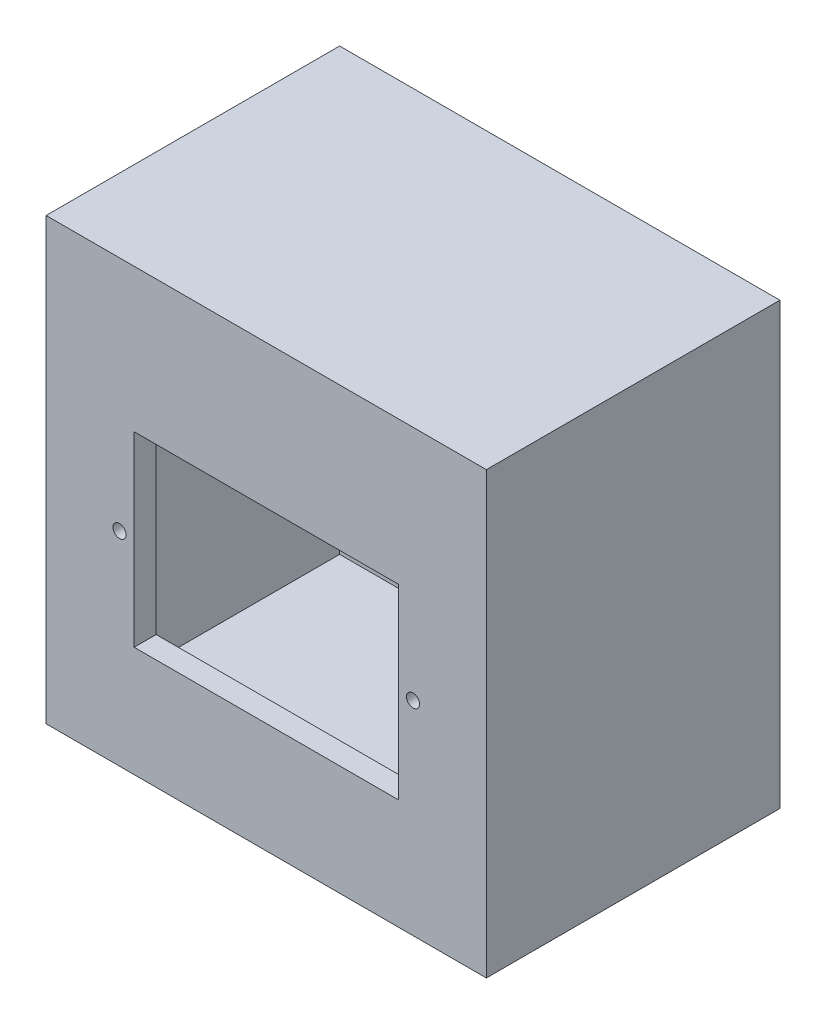
SolidWorks part; units mm, degrees
note: '?' marks a value the reader was unsure of.
ref_plane "Front Plane" through (0, 0, 0) normal (0, 0, 1) x (1, 0, 0)
ref_plane "Top Plane" through (0, 0, 0) normal (0, 1, 0) x (1, 0, 0)
ref_plane "Right Plane" through (0, 0, 0) normal (1, 0, 0) x (0, 0, -1)
sketch "Sketch1" plane through (0, 0, 0) normal (0, 1, 0) x (1, 0, 0)
  line L1 (-38.1, -25.4) -> (38.1, -25.4)
  line L2 (-38.1, -25.4) -> (-38.1, 25.4)
  line L3 (-38.1, 25.4) -> (38.1, 25.4)
  line L4 (38.1, -25.4) -> (38.1, 25.4)
  line L5 (-38.1, -25.4) -> (38.1, 25.4) construction
  line L6 (-38.1, 25.4) -> (38.1, -25.4) construction
  point P0 (0, 0)
  dimension "D1" = 50.8
  dimension "D2" = 76.2
extrude "body" add sketch "Sketch1" along normal blind 76.2
sketch "Sketch2" plane through (0, 0, 25.4) normal (0, 0, 1) x (1, 0, 0)
  line L0 (-38.1, 0) -> (38.1, 0) construction
  line L1 (-22.86, 19.0956) -> (22.86, 19.0956)
  line L2 (-22.86, 19.0956) -> (-22.86, 51.4044)
  line L3 (-22.86, 51.4044) -> (22.86, 51.4044)
  line L4 (22.86, 19.0956) -> (22.86, 51.4044)
  line L5 (-22.86, 19.0956) -> (22.86, 51.4044) construction
  line L6 (-22.86, 51.4044) -> (22.86, 19.0956) construction
  point P0 (0, 35.25)
  point P5 (0, 0)
  dimension "D1" = 32.3088
  dimension "D2" = 45.72
  dimension "D3" = 0
extrude "camera hole" cut sketch "Sketch2" against normal blind 3.81
shell "hollow" thickness 2.54 removed face at (0, 35.25, 21.59)
hole_wizard "#4-40 Tapped Hole1" positions "Sketch4" profile "Sketch3" tap size "#4-40" standard "ANSI Inch"
sketch "Sketch4" plane through (0, 0, 25.4) normal (0, 0, 1) x (1, 0, 0)
  line L1 (22.86, 51.4044) -> (-22.86, 51.4044) construction
  point P0 (-25.4, 35.25)
  point P2 (25.4, 35.25)
  point P14 (0, 51.4044)
  dimension "D1" = 50.8
  dimension "D2" = 25.4
  dimension "D3" = 16.1544
sketch "Sketch3" plane through (-25.4, 35.25, 25.4) normal (1, 0, 0) x (0, -1, 0)
  line L0 (0, 0) -> (0, 48.9382)
  line L1 (0, 48.9382) -> (1.1303, 48.259)
  line L2 (1.1303, 48.259) -> (1.1303, 0)
  line L5 (1.1303, 0) -> (0, 0)
  line L10 (0, 48.9382) -> (-1.1303, 48.259) construction
  line L11 (0, -6.35) -> (0, 107.95) construction
  dimension "Tap Drill Dia." = 2.2606
  dimension "Tap Drill Depth" = 48.259
  dimension "Drill Angle" = 118
sketch "Sketch5" plane through (0, 0, -25.4) normal (0, 0, -1) x (-1, 0, 0)
  line L0 (-38.1, 0) -> (38.1, 0) construction
  point P0 (-17.78, 41.2535)
  point P1 (17.78, 41.2535)
  point P2 (0, 0)
  dimension "D1" = 35.56
  dimension "D2" = 17.78
ref_axis "joystick axis" through (-17.78, 41.2535, -25.4) along (0, 0, -1)?
ref_axis "dpad axis" through (17.78, 41.2535, -25.4) along (0, 0, -1)?
sketch "Sketch6" plane through (0, 0, -25.4) normal (0, 0, -1) x (-1, 0, 0)
  circle A0 centre (-17.78, 34.9035) radius 2.794
  dimension "D1" = 5.588
  dimension "D2" = 6.35
extrude "one dpad leg hole" cut sketch "Sketch6" against normal up to next
pattern_circular "all dpad leg holes" count 4 over 360 about axis through (17.78, 41.2535, 0) along (0, 0, 1) of "one dpad leg hole"
sketch "Sketch7" plane through (0, 0, -25.4) normal (0, 0, -1) x (-1, 0, 0)
  circle A0 centre (17.78, 34.9035) radius 2.794
  dimension "D2" = 5.588
  dimension "D1" = 6.35
extrude "one joystick leg hole" cut sketch "Sketch7" against normal up to next
pattern_circular "all joystick leg holes" count 4 over 360 about axis through (-17.78, 41.2535, 0) along (0, 0, 1) of "one joystick leg hole"
